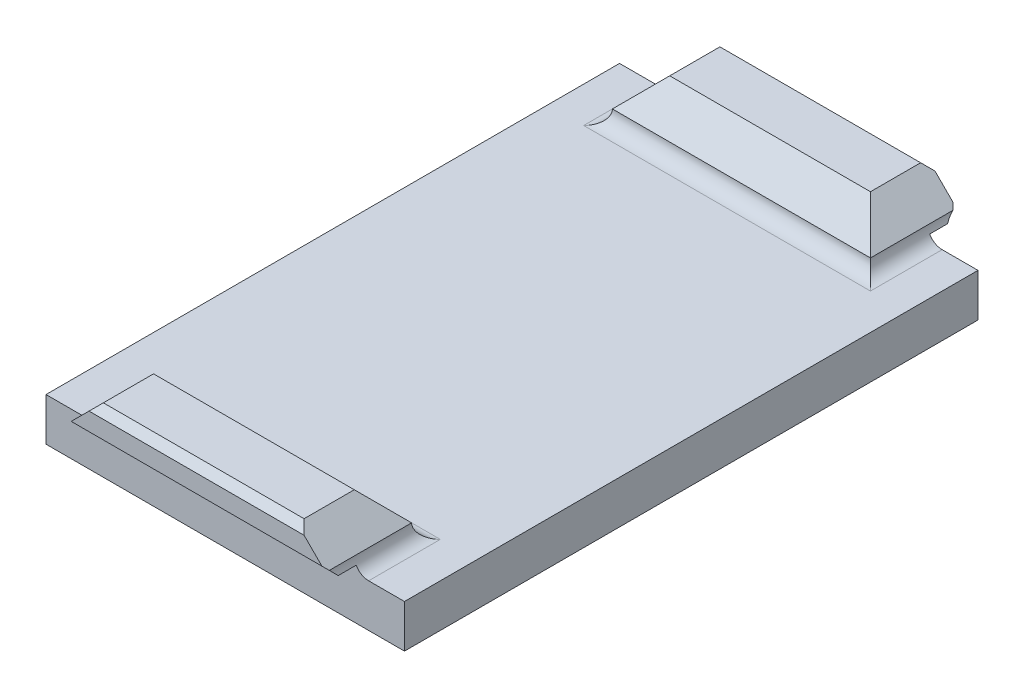
SolidWorks part; units mm, degrees
ref_plane "Front" through (0, 0, 0) normal (0, 0, 1) x (1, 0, 0)
ref_plane "Top" through (0, 0, 0) normal (0, 1, 0) x (1, 0, 0)
ref_plane "Right" through (0, 0, 0) normal (1, 0, 0) x (0, 0, -1)
sketch "Эскиз1" plane through (0, 0, 0) normal (0, 0, 1) x (1, 0, 0)
  line L1 (-17.0795, 18.39) -> (7.9205, 18.39)
  line L2 (-17.0795, 18.39) -> (-17.0795, 15.39)
  line L3 (-17.0795, 15.39) -> (7.9205, 15.39)
  line L4 (7.9205, 18.39) -> (7.9205, 15.39)
  dimension "D1" = 3
  dimension "D2" = 25
extrude "Бобышка-Вытянуть1" add sketch "Эскиз1" along normal blind 20
sketch "Эскиз2" plane through (0, 18.39, 0) normal (0, 1, 0) x (1, 0, 0)
  line L0 (7.9205, 0) -> (-17.0795, 0) construction
  line L1 (-13.5795, 0) -> (4.4205, 0)
  line L2 (-13.5795, 0) -> (-13.5795, -4)
  line L3 (-13.5795, -4) -> (4.4205, -4)
  line L4 (4.4205, 0) -> (4.4205, -4)
  line L5 (7.9205, -20) -> (7.9205, 0) construction
  line L6 (-17.0795, -20) -> (-17.0795, 0) construction
  dimension "D1" = 3.5
  dimension "D2" = 3.5
  dimension "D3" = 4
extrude "Бобышка-Вытянуть2" add sketch "Эскиз2" along normal blind 3
sketch "Эскиз3" plane through (0, 0, 0) normal (0, 0, -1) x (-1, 0, 0)
  line L0 (13.5795, 21.39) -> (13.5795, 18.39) construction
  line L1 (-4.4205, 21.39) -> (13.5795, 21.39)
  line L2 (-4.4205, 21.39) -> (-4.4205, 19.89)
  line L4 (13.5795, 21.39) -> (13.5795, 19.89)
  line L5 (-4.4205, 19.89) -> (-4.4205, 18.8965)
  line L6 (-4.4205, 21.39) -> (-4.4205, 18.39) construction
  line L7 (-4.4205, 18.8965) -> (13.5795, 18.8965)
  line L8 (13.5795, 18.8965) -> (13.5795, 19.89)
extrude "Бобышка-Вытянуть3" add sketch "Эскиз3" along normal blind 2
chamfer "Фаска1" distance 0.75 angle 45 1 edges at (-4.5795, 18.8965, -2)
chamfer "Фаска2" distance 0.5 angle 45 1 edges at (-4.5795, 21.39, -2)
chamfer "Фаска3" distance 2 angle 45 1 edges at (-4.5795, 21.39, 4)
mirror "Зеркальное отражение1" about plane through (0, 0, 20) normal (0, 0, 1) of bodies 103
chamfer "Chamfer1" distance 2 angle 45 4 edges at (4.4205, 21.39, 39.75) (-13.5795, 21.39, 39.75) (4.4205, 21.39, 0.25) (-13.5795, 21.39, 0.25)
fillet "Fillet1" radius 1 6 edges at (-4.5795, 18.39, 4) (-4.5795, 18.39, 36) (-13.5795, 18.39, 2) (4.4205, 18.39, 2) (4.4205, 18.39, 38) (-13.5795, 18.39, 38)
